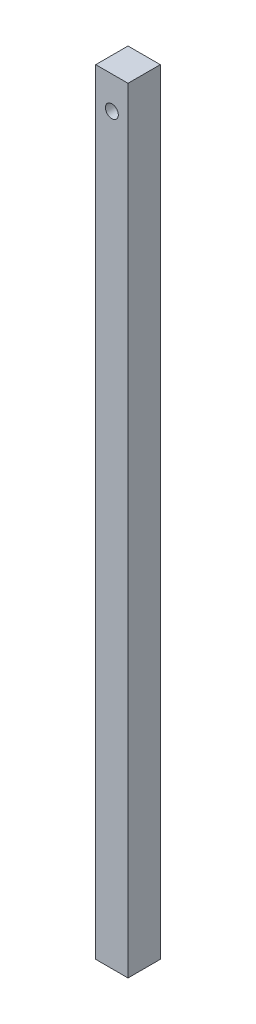
SolidWorks part; units mm, degrees
material "Brass"
ref_plane "Front Plane" through (0, 0, 0) normal (0, 0, 1) x (1, 0, 0)
ref_plane "Top Plane" through (0, 0, 0) normal (0, 1, 0) x (1, 0, 0)
ref_plane "Right Plane" through (0, 0, 0) normal (1, 0, 0) x (0, 0, -1)
sketch "Sketch1" plane through (0, 0, 0) normal (0, 0, 1) x (1, 0, 0)
  line L0 (-2.5, 0) -> (2.5, 0)
  line L1 (2.5, 0) -> (2.5, 120)
  line L2 (2.5, 120) -> (-2.5, 120)
  line L3 (-2.5, 120) -> (-2.5, 0)
extrude "Boss-Extrude1" add sketch "Sketch1" along normal blind 5
sketch "Sketch2" plane through (0, 0, 0) normal (0, 0, 1) x (1, 0, 0)
  circle A0 centre (0, 115) radius 1
  dimension "D1" = 2
extrude "Cut-Extrude1" cut sketch "Sketch2" against normal mid plane 20
